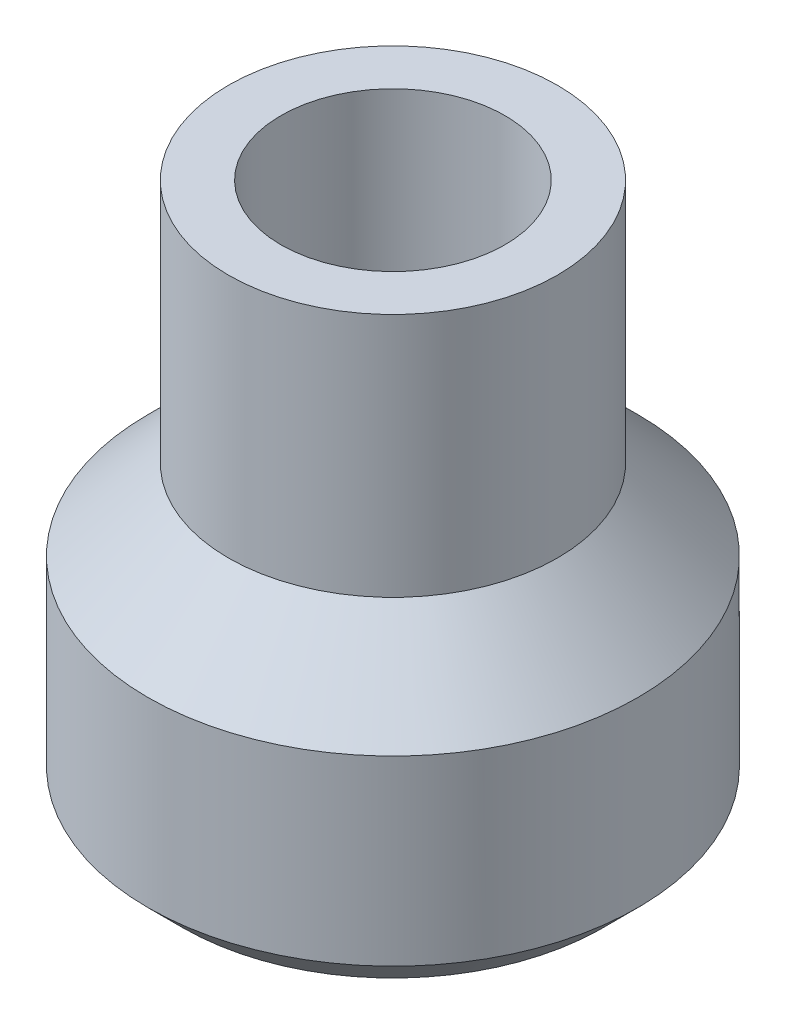
SolidWorks part; units mm, degrees
ref_plane "Front Plane" through (0, 0, 0) normal (0, 0, 1) x (1, 0, 0)
ref_plane "Top Plane" through (0, 0, 0) normal (0, 1, 0) x (1, 0, 0)
ref_plane "Right Plane" through (0, 0, 0) normal (1, 0, 0) x (0, 0, -1)
sketch "Sketch1" plane through (0, 0, 0) normal (0, 1, 0) x (1, 0, 0)
  circle A0 centre (0, 0) radius 4.7
  circle A1 centre (0, 0) radius 3.2
  dimension "D1" = 1.5
  dimension "D2" = 6.4
extrude "Boss-Extrude1" add sketch "Sketch1" along normal blind 10
sketch "Sketch2" plane through (0, 0, 0) normal (0, 1, 0) x (1, 0, 0)
  circle A0 centre (0, 0) radius 7
  dimension "D1" = 14
extrude "Boss-Extrude2" add sketch "Sketch2" against normal blind 6
sketch "Sketch3" plane through (0, -6, 0) normal (0, -1, 0) x (1, 0, 0)
  circle A0 centre (0, 0) radius 6
  dimension "D1" = 12
extrude "Cut-Extrude1" cut sketch "Sketch3" against normal offset from surface (4 mm away) 2 up to face at (0, 0, 4.7)
sketch "Sketch4" plane through (0, 0, 0) normal (0, 1, 0) x (1, 0, 0)
  circle A0 centre (0, 0) radius 3.2
  circle A1 centre (0, 0) radius 3.2 construction
extrude "Cut-Extrude2" cut sketch "Sketch4" against normal through all
ref_plane "Plane1" through (0, -6, 0) normal (0, -1, 0) x (-1, 0, 0)
chamfer "Chamfer2" distance 1.5 angle 45 1 edges at (0, -6, 7)
chamfer "Chamfer4" distance 3 angle 45 1 edges at (0, 0, 4.7)
chamfer "Chamfer5" distance 1 angle 45 1 edges at (0, -2, 3.2)
